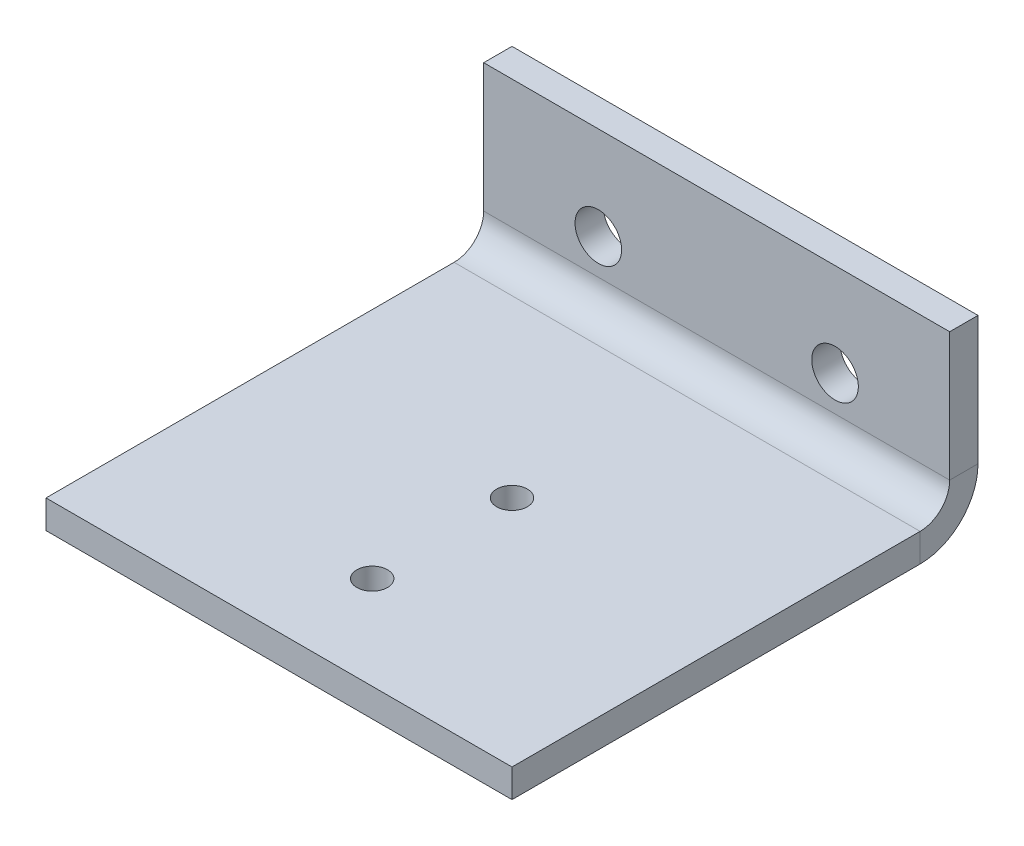
SolidWorks part; units mm, degrees
note: The reader was unsure of these and kept them because the rebuilt part matched: flange length of "Brida de arista1".
ref_plane "Alzado" through (0, 0, 0) normal (0, 0, 1) x (1, 0, 0)
ref_plane "Planta" through (0, 0, 0) normal (0, 1, 0) x (1, 0, 0)
ref_plane "Vista lateral" through (0, 0, 0) normal (1, 0, 0) x (0, 0, -1)
sketch "Croquis1" plane through (0, 0, 0) normal (0, 0, 1) x (1, 0, 0)
  line L0 (0, 0) -> (-12.7, 0) construction
  line L1 (-25, 10) -> (25, 10)
  line L2 (-25, 10) -> (-25, -10)
  line L3 (-25, -10) -> (25, -10)
  line L4 (25, 10) -> (25, -10)
  line L5 (-25, 10) -> (25, -10) construction
  line L6 (-25, -10) -> (25, 10) construction
  line L7 (0, 0) -> (12.7, 0) construction
  circle A0 centre (-12.7, 0) radius 2.5
  circle A1 centre (12.7, 0) radius 2.5
  point P0 (0, 0)
  dimension "D5" = 5
  dimension "D6" = 5
  dimension "D1" = 20
  dimension "D2" = 50
  dimension "D3" = 12.7
  dimension "D4" = 12.7
base flange "Brida base1" sketch "Croquis1" thickness 3.0378 reverse thickness direction no parameters "D1"=3.175
edge flange "Brida de arista1" sketch "Croquis8" flange angle 90 flange length 50 flange position material inside bend radius 3.175 thickness 3.0378 relief rectangular parameters "D6"=10
sketch "Croquis8" plane through (0, -10, 0) normal (0, -1, 0) x (1, 0, 0)
  line L0 (-25, 0) -> (25, 0) construction
  line L1 (-25, 0) -> (25, 0)
  line L2 (-25, 0) -> (-25, 46.9622)
  line L3 (-25, 46.9622) -> (25, 46.9622)
  line L4 (25, 46.9622) -> (25, 0)
bend "Pliegue de arista1" bend radius 3.175 bend angle 90 parameters "D5"=1
sketch "Croquis9" plane through (0, -10, 0) normal (0, -1, 0) x (-1, 0, 0)
  line L0 (0, -36.9622) -> (0, -21.9622) construction
  line L1 (-25, -46.9622) -> (25, -46.9622) construction
  line L2 (0, -46.9622) -> (0, -36.9622) construction
  circle A2 centre (0, -36.9622) radius 1.65
  circle A3 centre (0, -21.9622) radius 1.65
  dimension "D2" = 3.3
  dimension "D3" = 3.3
  dimension "D1" = 15
  dimension "D4" = 10
extrude "Cortar-Extruir1" cut sketch "Croquis9" against normal up to next normal cut yes
sketch "Líneas de pliegue1" [suppressed] plane through (0, 0, 0) normal (0, 1, 0) x (1, 0, 0)
sketch "Cuadro delimitador1" [suppressed] plane through (0, 0, 0) normal (0, 1, 0) x (1, 0, 0)
sheet metal parameters "Chapa metálica1" thickness 3.0378 parameters "D1"=3.175
flat pattern "Chapa desplegada1" [suppressed]
sketch "Líneas de pliegue2" plane through (0, 0, 0) normal (0, 1, 0) x (1, 0, 0)
sketch3d "Cuadro delimitador2" [suppressed]
  line L0 (25, -10, 0) -> (-25, -10, 0) construction
  line L1 (25, 10, 0) -> (-25, 10, 0) construction
  line L2 (25, -10, 0) -> (25, 10, 0) construction
  line L3 (-25, -10, 0) -> (-25, 10, 0) construction
sheet metal parameters "Chapa metálica2" thickness 3.0378 parameters "D1"=3.175
flat pattern "Chapa desplegada1"
sketch "Líneas de pliegue2" plane through (0, 0, 0) normal (0, 0, 1) x (1, 0, 0)
  line L0 (-25, -7.4738) -> (25, -7.4738) construction
  line L1 (-25, -7.4738) -> (25, -7.4738) construction
sketch3d "Cuadro delimitador2" [suppressed]
  line L0 (25, 10, 0) -> (25, -54.9475, 0) construction
  line L1 (-25, 10, 0) -> (-25, -54.9475, 0) construction
  line L2 (25, 10, 0) -> (-25, 10, 0) construction
  line L3 (25, -54.9475, 0) -> (-25, -54.9475, 0) construction
bend of the flat pattern "Aplanar-<Pliegue de arista1>1"
sheet metal parameters "Chapa metálica3" thickness 3.0378 parameters "D1"=3.175
flat pattern "Chapa desplegada1"
sketch "Líneas de pliegue2" plane through (0, 0, 0) normal (0, 0, 1) x (1, 0, 0)
  line L0 (-25, -7.4738) -> (25, -7.4738) construction
  line L1 (-25, -7.4738) -> (25, -7.4738) construction
sketch3d "Cuadro delimitador2" [suppressed]
  line L0 (25, 10, 0) -> (25, -54.9475, 0) construction
  line L1 (-25, 10, 0) -> (-25, -54.9475, 0) construction
  line L2 (25, 10, 0) -> (-25, 10, 0) construction
  line L3 (25, -54.9475, 0) -> (-25, -54.9475, 0) construction
bend of the flat pattern "Aplanar-<Pliegue de arista1>1"
